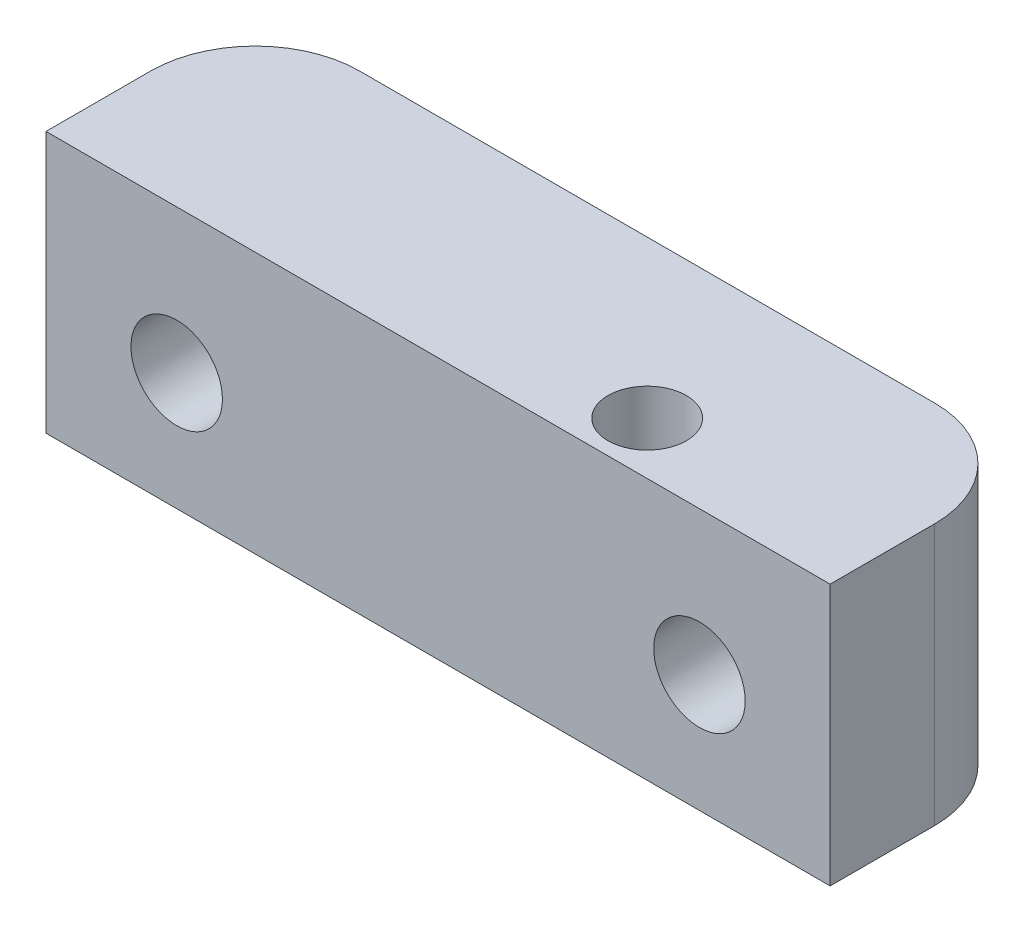
SolidWorks part; units mm, degrees
ref_plane "Front Plane" through (0, 0, 0) normal (0, 0, 1) x (1, 0, 0)
ref_plane "Top Plane" through (0, 0, 0) normal (0, 1, 0) x (1, 0, 0)
ref_plane "Right Plane" through (0, 0, 0) normal (1, 0, 0) x (0, 0, -1)
sketch "Sketch1" plane through (0, 0, 0) normal (0, 1, 0) x (1, 0, 0)
  line L0 (6, -2) -> (6, -4) construction
  line L5 (-15, 4) -> (15, 4)
  line L6 (-15, 4) -> (-15, -4)
  line L7 (-15, -4) -> (15, -4)
  line L8 (15, 4) -> (15, -4)
  line L9 (-15, 4) -> (15, -4) construction
  line L10 (-15, -4) -> (15, 4) construction
  line L11 (0, 0) -> (6, 0) construction
  circle A0 centre (6, -2) radius 1.5
  point P0 (0, 0)
  dimension "D3" = 3
  dimension "D1" = 30
  dimension "D2" = 8
  dimension "D4" = 2
  dimension "D5" = 6
extrude "Boss-Extrude1" add sketch "Sketch1" along normal blind 2
sketch "Sketch2" plane through (0, 0, 4) normal (0, 0, 1) x (1, 0, 0)
  line L0 (-10, -3.5) -> (10, -3.5) construction
  line L2 (-15, 0) -> (-15, -8)
  line L5 (15, 0) -> (5, 0)
  line L6 (15, 0) -> (15, -8)
  line L7 (15, -8) -> (-15, -8)
  line L9 (-15, 0) -> (5, 0)
  line L10 (-15, 2) -> (15, 2) construction
  line L11 (-15, 0) -> (15, 0) construction
  circle A0 centre (-10, -3.5) radius 1.75
  circle A1 centre (10, -3.5) radius 1.75
  point P13 (10, 0)
  point P17 (0, -3.5)
  point P22 (0, 0)
  dimension "D1" = 3.5
  dimension "D2" = 3.5
  dimension "D3" = 5.5
  dimension "D4" = 8
  dimension "D5" = 20
extrude "Boss-Extrude2" add sketch "Sketch2" against normal up to surface (8 mm away) up to face at (0, 1, -4)
sketch "Sketch4" plane through (0, 0, 0) normal (0, 1, 0) x (1, 0, 0)
  circle A1 centre (6, -2) radius 1.5
  circle A2 centre (6, -2) radius 1.5
  dimension "D1" = 0
extrude "Cut-Extrude2" cut sketch "Sketch4" against normal through all
fillet "Fillet1" radius 4 2 edges at (15, -3, -4) (-15, -3, -4)
